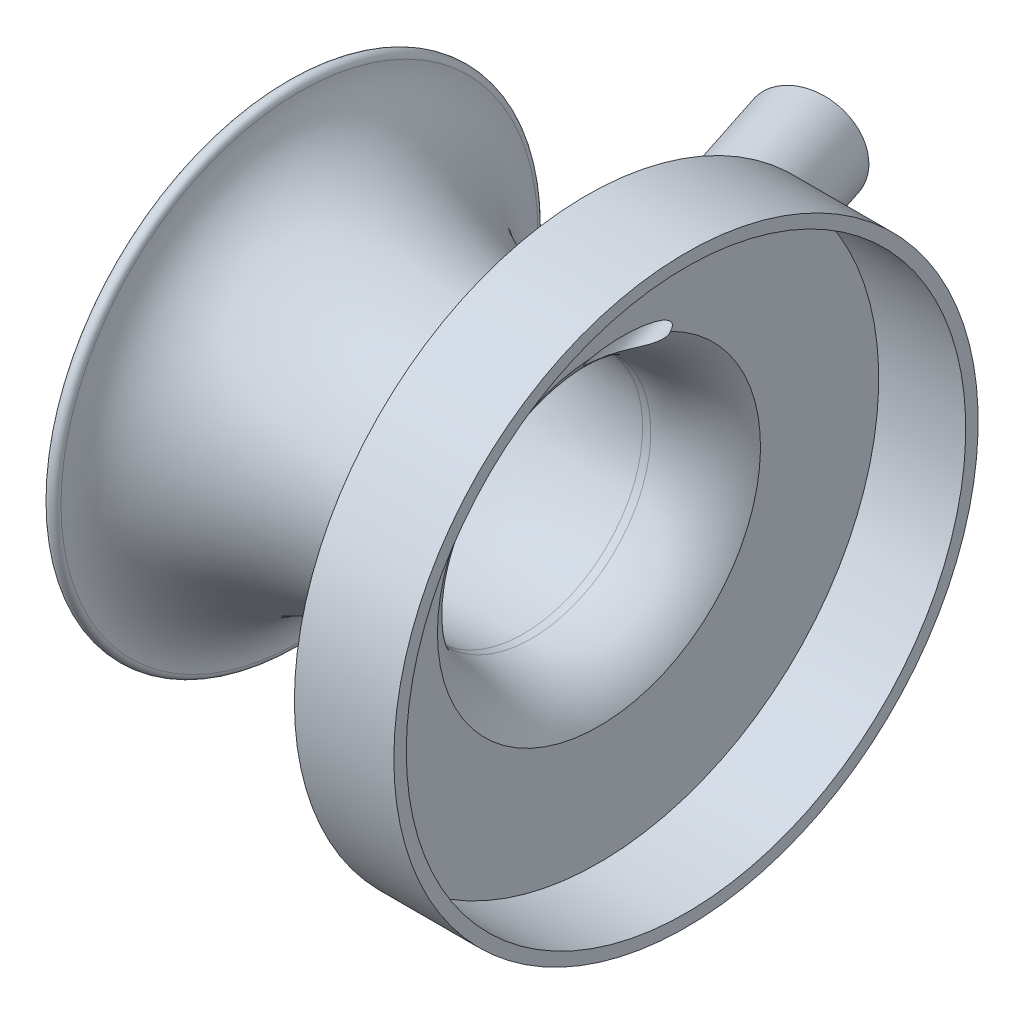
SolidWorks part; units mm, degrees
material "PVC 0.007 Plasticized"
ref_plane "Front Plane" through (0, 0, 0) normal (0, 0, 1) x (1, 0, 0)
ref_plane "Top Plane" through (0, 0, 0) normal (0, 1, 0) x (1, 0, 0)
ref_plane "Right Plane" through (0, 0, 0) normal (1, 0, 0) x (0, 0, -1)
sketch "Sketch1" plane through (0, 0, 0) normal (0, 0, 1) x (1, 0, 0)
  line L0 (-17.78, 33.4033) -> (-17.78, 57.5533)
  line L1 (-34.3222, 33.4033) -> (-9.5791, 33.4033) construction
  line L3 (-34.3222, 0.4033) -> (53.9483, 0.4033) construction
  line L11 (-33.2131, 24.7619) -> (-31.5799, 24.7915)
  line L12 (-17.78, 57.5533) -> (0, 57.5533)
  line L13 (-33.2365, 27.3019) -> (-31.68, 27.3301)
  line L14 (-20.32, 34.0999) -> (-20.32, 60.0933)
  line L15 (-20.32, 60.0933) -> (0, 60.0933)
  line L16 (0, 60.0933) -> (0, 57.5533)
  circle A4 centre (-32.5832, 41.7619) radius 17 construction
  arc A5 (-17.78, 33.4033) -> (-31.5799, 24.7915) centre (-32.5832, 41.7619) cw
  arc A6 (-20.32, 34.0999) -> (-31.68, 27.3301) centre (-32.5832, 41.7619) cw
  arc A7 (-81.5276, 49.1004) -> (-78.9876, 49.1015) centre (-80.2576, 49.101) cw
  ellipse E0 centre (-33.2232, 49.1205) end of major axis (-81.5276, 49.1004) minor radius 24.3586 (-81.5276, 49.1004) -> (-33.2131, 24.7619) ccw
  ellipse E1 centre (-33.2232, 49.1205) end of major axis (-81.5276, 49.1004) minor radius 24.3586 construction
  spline S0 degree 1 poles (-78.9876, 49.1015) (-33.2365, 27.3019) knots 0 0 1 1 construction
  spline S1 degree 3 poles (-78.9876, 49.1015) (-78.9874, 48.4651) (-78.8643, 47.2068) (-78.1154, 44.6473) (-76.1728, 41.3828) (-72.1247, 37.5428) (-66.4667, 34.0595) (-59.4331, 31.146) (-51.3175, 28.9592) (-42.4745, 27.6059) (-36.296, 27.3013) (-33.2365, 27.3019) knots 3.141593 3.141593 3.141593 3.141593 3.239738 3.337883 3.534173 3.730463 3.926753 4.123043 4.319333 4.515623 4.711913 4.711913 4.711913 4.711913
  dimension "D3" = 24.3586
  dimension "D1" = 33.0001
  dimension "D2" = 15.4432
  dimension "D4" = 48.3044
  dimension "D5" = 57.15
  dimension "D10" = 34
  dimension "D11" = 17
  dimension "D6" = 17.78
  dimension "D8" = 24.3586
  dimension "D7" = 2.54
revolve "Revolve1" add sketch "Sketch1" angle 360 about L3
ref_axis "Axis1" through (0, 65.659, 0) along (0, -1, 0)
ref_plane "Plane1" through (0, 0, 0) normal (-0.309, 0, -0.9511) x (0, -1, 0)
ref_plane "Plane2" through (-13.3434, 0, -41.0666) normal (-0.309, 0, -0.9511) x (0, -1, 0)
sketch "Sketch2" plane through (-13.3434, 0, -41.0666) normal (-0.309, 0, -0.9511) x (0, -1, 0)
  line L0 (-33.0001, 18.6255) -> (-26.9006, 18.6255) construction
  circle A0 centre (-30.8893, 15.4505) radius 3.175
  circle A1 centre (-30.8893, 15.4505) radius 10.16
  circle A2 centre (-30.8893, 15.4505) radius 5.5562
  ellipse E0 centre (0, 18.6255) end of major axis (-33.0001, 18.6255) minor radius 9.0224 construction
  dimension "D1" = 6.35
  dimension "D2" = 20.32
  dimension "D3" = 11.1125
  dimension "D4" = 0
extrude "Boss-Extrude1" add sketch "Sketch2" against normal up to next separate body contours A2 A0 region at (-28.0376, 36.2884, -36.2922)
extrude "Cut-Extrude1" cut sketch "Sketch2<3>" along direction (-0.309, 0, -0.9511) on the side against the normal blind 40.64 and the other way through all contours A0 region at (-28.0376, 30.8893, -36.2922)
sketch "Sketch2<3>" plane through (-13.3434, 0, -41.0666) normal (-0.309, 0, -0.9511) x (0, -1, 0) same geometry as "Sketch2"
extrude "Boss-Extrude3" add sketch "Sketch2<4>" against normal blind 1.016 and the other way blind 25.4 contours A1 A2 region at (-28.0376, 40.7619, -36.2922)
sketch "Sketch2<4>" plane through (-13.3434, 0, -41.0666) normal (-0.309, 0, -0.9511) x (0, -1, 0) same geometry as "Sketch2"
